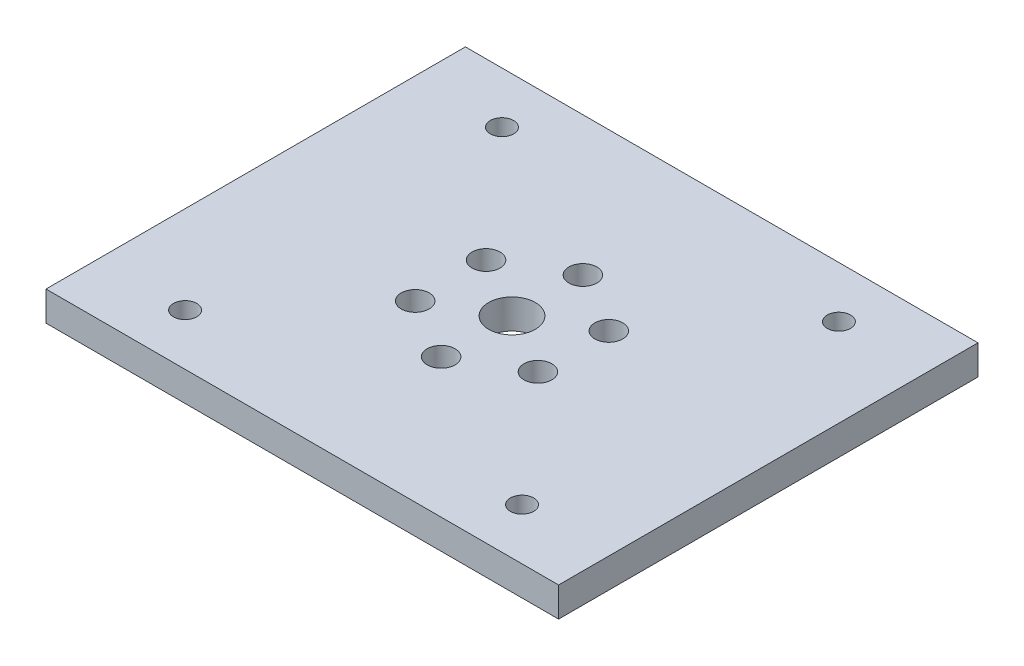
SolidWorks part; units mm, degrees
material "6061 Alloy"
ref_plane "Front Plane" through (0, 0, 0) normal (0, 0, 1) x (1, 0, 0)
ref_plane "Top Plane" through (0, 0, 0) normal (0, 1, 0) x (1, 0, 0)
ref_plane "Right Plane" through (0, 0, 0) normal (1, 0, 0) x (0, 0, -1)
sketch "Sketch2" plane through (0, 0, 0) normal (0, 1, 0) x (1, 0, 0)
  line L0 (0, 0) -> (0, 90)
  line L1 (0, 90) -> (110, 90)
  line L2 (110, 90) -> (110, 0)
  line L3 (110, 0) -> (0, 0)
  dimension "D1" = 110
  dimension "D2" = 90
extrude "Boss-Extrude1" add sketch "Sketch2" along normal blind 6.35
sketch "Sketch3" plane through (0, 6.35, 0) normal (0, 1, 0) x (1, 0, 0)
  line L1 (110, 90) -> (0, 90) construction
  line L2 (0, 0) -> (110, 0) construction
  line L4 (55, 90) -> (55, 0) construction
  line L5 (0, 45) -> (55, 45) construction
  line L6 (55, 45) -> (110, 45) construction
  line L7 (0, 90) -> (0, 0) construction
  circle A0 centre (18.85, 79) radius 2.5
  circle A1 centre (18.85, 11) radius 2.5
  circle A2 centre (91.15, 11) radius 2.5
  circle A3 centre (91.15, 79) radius 2.5
  dimension "D4" = 5
  dimension "D3" = 11
  dimension "D2" = 18.85
extrude "Mounting Holes" cut sketch "Sketch3" against normal through all
sketch "Sketch5" plane through (0, 6.35, 0) normal (0, 1, 0) x (1, 0, 0)
  line L0 (55, 90) -> (55, 0) construction
  line L1 (110, 90) -> (0, 90) construction
  line L2 (0, 0) -> (110, 0) construction
  line L3 (0, 45) -> (110, 45) construction
  line L4 (0, 90) -> (0, 0) construction
  line L5 (110, 0) -> (110, 90) construction
  circle A0 centre (55, 45) radius 15.21 construction
  circle A1 centre (55, 60.21) radius 3
  circle A2 centre (68.1722, 52.605) radius 3
  circle A3 centre (68.1722, 37.395) radius 3
  circle A4 centre (55, 29.79) radius 3
  circle A5 centre (41.8278, 37.395) radius 3
  circle A6 centre (41.8278, 52.605) radius 3
  circle A7 centre (55, 45) radius 5
  dimension "D1" = 30.42
  dimension "D2" = 6
  dimension "D4" = 10
  dimension "D3" = 6
extrude "Cut-Extrude1" cut sketch "Sketch5" against normal up to next
equation "\"L1L\"=500"
equation "\"L1Thick\"=6.35"
equation "\"Harm-Drive-Outer\"=74.5"
equation "\"L1-Spacing\"=100"
equation "\"L-Bracket-HoleToWall\"=12.5"
equation "\"D3@Sketch3\"=\"L-Bracket-HoleToSide\""
equation "\"L-Bracket-HoleToSide\"=11"
equation "\"Bracket-Hole-D\"=6.8"
equation "\"L1-Spacing\"=115.65"
equation "\"D2@Sketch3\"=\"L-Bracket-HoleToWall\"+\"L1Thick\""
